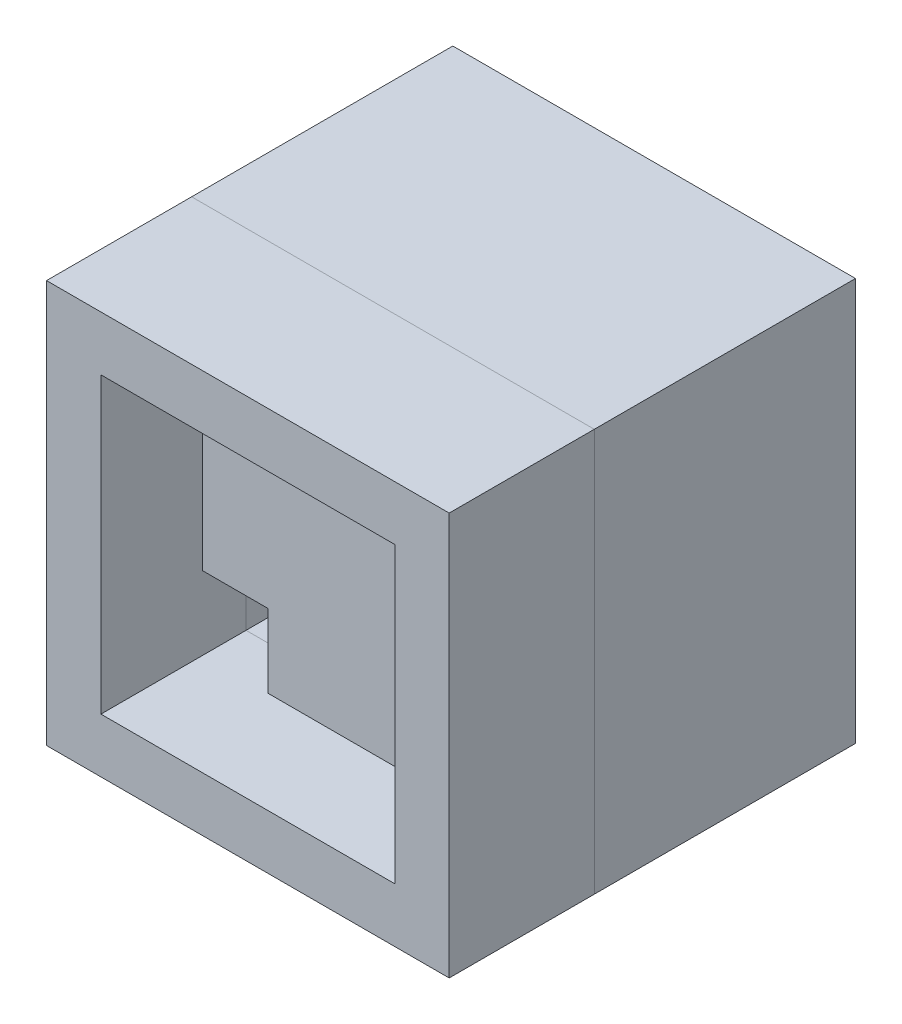
SolidWorks part; units mm, degrees
ref_plane "Front Plane" through (0, 0, 0) normal (0, 0, 1) x (1, 0, 0)
ref_plane "Top Plane" through (0, 0, 0) normal (0, 1, 0) x (1, 0, 0)
ref_plane "Right Plane" through (0, 0, 0) normal (1, 0, 0) x (0, 0, -1)
sketch "Sketch1" plane through (0, 0, 0) normal (0, 0, 1) x (1, 0, 0)
  line L0 (1.5, 9.6) -> (9.6, 1.5) construction
  line L1 (0, 0) -> (11.1, 0)
  line L2 (0, 0) -> (0, 11.1)
  line L3 (0, 11.1) -> (11.1, 11.1)
  line L4 (11.1, 0) -> (11.1, 11.1)
  line L5 (1.5, 1.5) -> (9.6, 1.5)
  line L6 (1.5, 1.5) -> (1.5, 9.6)
  line L7 (1.5, 9.6) -> (9.6, 9.6)
  line L8 (9.6, 1.5) -> (9.6, 9.6)
  line L9 (3.15, 7.95) -> (1.5, 7.95) construction
  line L10 (2.775, 8.325) -> (3.525, 8.325) construction
  line L11 (2.775, 8.325) -> (2.775, 7.575) construction
  line L12 (2.775, 7.575) -> (3.525, 7.575) construction
  line L13 (3.525, 8.325) -> (3.525, 7.575) construction
  line L14 (1.5, 7.95) -> (3.15, 7.95) construction
  line L15 (3.15, 7.95) -> (3.15, 9.6) construction
  line L16 (0, 5.55) -> (1.5, 5.55) construction
  line L17 (1.5, 7.575) -> (3.3, 7.575)
  line L18 (1.5, 7.575) -> (1.5, 9.6)
  line L19 (1.5, 9.6) -> (3.3, 9.6)
  line L20 (3.3, 7.575) -> (3.3, 9.6)
  line L21 (7.8, 9.6) -> (9.6, 9.6)
  line L22 (7.8, 9.6) -> (7.8, 7.575)
  line L23 (7.8, 7.575) -> (9.6, 7.575)
  line L24 (9.6, 9.6) -> (9.6, 7.575)
  line L25 (1.5, 3.525) -> (3.3, 3.525)
  line L26 (1.5, 3.525) -> (1.5, 1.5)
  line L27 (1.5, 1.5) -> (3.3, 1.5)
  line L28 (3.3, 3.525) -> (3.3, 1.5)
  line L29 (9.6, 3.525) -> (7.8, 3.525)
  line L30 (9.6, 3.525) -> (9.6, 1.5)
  line L31 (9.6, 1.5) -> (7.8, 1.5)
  line L32 (7.8, 3.525) -> (7.8, 1.5)
  line L33 (5.55, 9.6) -> (5.55, 11.1) construction
  point P15 (3.15, 8.325)
  dimension "D1" = 1.65
  dimension "D2" = 0.75
  dimension "D3" = 1.5
  dimension "D4" = 8.1
  dimension "D5" = 1.8
  dimension "D6" = 11.1
extrude "Boss-Extrude1" add sketch "Sketch1" along normal blind 1.2 contours L3 L4 L1 L2
ref_plane "Plane2" through (0, 0, 1.2) normal (0, 0, 1) x (1, 0, 0)
extrude "Boss-Extrude2" add sketch "Sketch1<3>" along normal blind 10 from surface contours L1 L4 L3 L2 L8 L5 L6 L7 region at (0.157, 5.55, 0) starting at face at (5.55, 5.55, 1.2)
sketch "Sketch1<3>" plane through (0, 0, 0) normal (0, 0, 1) x (1, 0, 0) same geometry as "Sketch1"
ref_plane "Plane1" through (0, 0, 8.4) normal (0, 0, 1) x (1, 0, 0)
extrude "Boss-Extrude3" add sketch "Sketch1<4>" against normal blind 1.2 from surface contours L1 L4 L3 L2 L8 L5 L6 L7 | L32 L29 L8 L23 L22 L7 L20 L17 L6 L25 L28 L5 region at (0.157, 5.55, 0) region at (5.55, 5.55, 0) starting at plane "Plane1"
sketch "Sketch1<4>" plane through (0, 0, 0) normal (0, 0, 1) x (1, 0, 0) same geometry as "Sketch1"
split "Split2" bodies to split 103 resulting bodies 106 107 split by face at (5.55, 5.55, 7.2)
sketch "Sketch2" plane through (0, 0, 1.2) normal (0, 0, 1) x (1, 0, 0)
  line L1 (3.525, 0) -> (3.525, 1.5)
  line L2 (3.525, 0) -> (7.575, 0)
  line L3 (7.575, 0) -> (7.575, 1.5)
  line L4 (3.525, 1.5) -> (7.575, 1.5)
  line L7 (7.575, 0.75) -> (11.1, 0.75) construction
  line L8 (3.525, 0.75) -> (0, 0.75) construction
  line L11 (0, 11.1) -> (0, 0) construction
  line L12 (11.1, 11.1) -> (11.1, 0) construction
  line L13 (11.1, 0) -> (0, 0) construction
  line L15 (9.6, 1.5) -> (1.5, 1.5) construction
  dimension "D1" = 4.05
extrude "Cut-Extrude1" cut sketch "Sketch2" along normal blind 4
